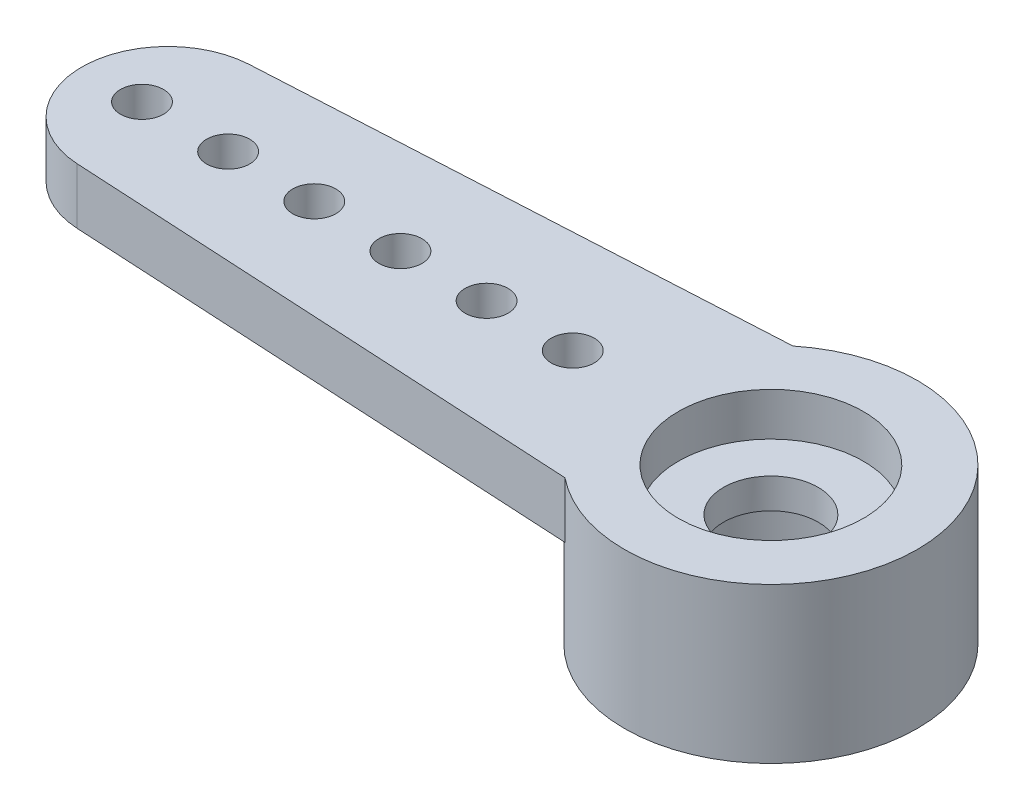
SolidWorks part; units mm, degrees
ref_plane "Płaszczyzna przednia" through (0, 0, 0) normal (0, 0, 1) x (1, 0, 0)
ref_plane "Płaszczyzna górna" through (0, 0, 0) normal (0, 1, 0) x (1, 0, 0)
ref_plane "Płaszczyzna prawa" through (0, 0, 0) normal (1, 0, 0) x (0, 0, -1)
sketch "Sketch1" plane through (0, 0, 0) normal (0, 1, 0) x (1, 0, 0)
  line L9 (3.7667, 8.32) -> (-8.2085, 7.6696)
  line L10 (-8.2085, 3.6754) -> (3.7667, 3.025)
  circle A1 centre (-8.7, 5.6725) radius 0.5
  arc A9 (3.7667, 3.025) -> (3.7667, 8.32) centre (5.9, 5.6725) ccw
  arc A10 (-8.2085, 7.6696) -> (-8.2085, 3.6754) centre (-8.1, 5.6725) ccw
  circle A13 centre (1.3, 5.6725) radius 0.5
  circle A14 centre (-0.7, 5.6725) radius 0.5
  circle A15 centre (-2.7, 5.6725) radius 0.5
  circle A16 centre (-4.7, 5.6725) radius 0.5
  circle A17 centre (-6.7, 5.6725) radius 0.5
  circle A19 centre (5.9, 5.6725) radius 1.1
  dimension "D1" = 1
  dimension "D2" = 2.2
  dimension "D3" = 3.4
  dimension "D4" = 2
  dimension "D5" = 1.3
  dimension "D6" = 3.7667
  dimension "D7" = 5.9
  dimension "D8" = 0.7
  dimension "D9" = 2.7
  dimension "D10" = 4.7
  dimension "D11" = 6.7
  dimension "D12" = 8.1
  dimension "D13" = 3.025
  dimension "D14" = 8.7
extrude "Boss-Extrude1" add sketch "Sketch1" against normal blind 1.3
sketch "Sketch3" plane through (0, 0, 0) normal (0, 1, 0) x (1, 0, 0)
  circle A1 centre (5.9, 5.6725) radius 2.15
  circle A3 centre (5.9, 5.6725) radius 1.1 construction
  dimension "D1" = 4.3
extrude "Cut-Extrude1" cut sketch "Sketch3" against normal blind 1
sketch "Sketch4" plane through (0, -1.3, 0) normal (0, -1, 0) x (1, 0, 0)
  circle A1 centre (5.9, -5.6725) radius 3.4
  circle A2 centre (1.3, -5.6725) radius 0.5 construction
  point P0 (5.9, -5.6725)
  point P3 (5.596, 1.1199)
  dimension "D1" = 6.8
  dimension "D2" = 4.296
  dimension "D3" = 6.7924
extrude "Boss-Extrude3" add sketch "Sketch4" along normal offset from surface (2.3 mm away) 3.6 up to face at (5.9, 0, -3.5225)
sketch "Sketch5" plane through (0, -3.6, 0) normal (0, -1, 0) x (1, 0, 0)
  circle A1 centre (5.9, -5.6725) radius 2.35
  arc A3 (3.7667, -8.32) -> (3.7667, -3.025) centre (5.9, -5.6725) ccw construction
  dimension "D1" = 4.7
extrude "Cut-Extrude2" cut sketch "Sketch5" against normal blind 1.9
sketch "Sketch6" plane through (0, -1.3, 0) normal (0, 1, 0) x (1, 0, 0)
  circle A1 centre (5.9, 5.6725) radius 1.1
  circle A2 centre (5.9, 5.6725) radius 1.1
  dimension "D1" = 0
extrude "Cut-Extrude3" cut sketch "Sketch6" against normal up to next
ref_axis "os obrotu" through (5.9, -9.5043, -5.6725) along (0, 1, 0)
ref_axis "Axis2" through (-11.5848, 0, -5.6725) along (1, 0, 0)
